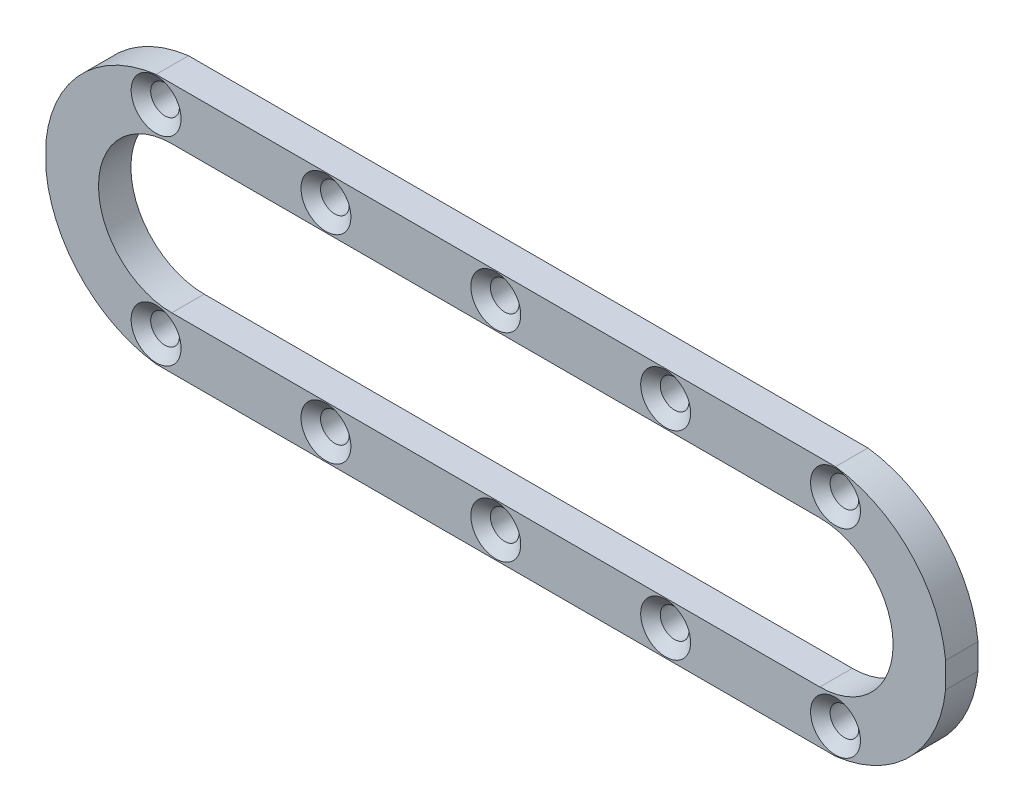
SolidWorks part; units mm, degrees
ref_plane "Front" through (0, 0, 0) normal (0, 0, 1) x (1, 0, 0)
ref_plane "Top" through (0, 0, 0) normal (0, 1, 0) x (1, 0, 0)
ref_plane "Right" through (0, 0, 0) normal (1, 0, 0) x (0, 0, -1)
sketch "Sketch1" plane through (0, 0, 0) normal (0, 0, 1) x (1, 0, 0)
  line L1 (88.138, 24.5745) -> (-88.138, 24.5745)
  line L2 (88.138, 24.5745) -> (88.138, -24.5745)
  line L3 (88.138, -24.5745) -> (-88.138, -24.5745)
  line L4 (-88.138, 24.5745) -> (-88.138, -24.5745)
  line L5 (88.138, 24.5745) -> (-88.138, -24.5745) construction
  line L6 (88.138, -24.5745) -> (-88.138, 24.5745) construction
  point P0 (0, 0)
  dimension "D1" = 176.276
  dimension "D2" = 49.149
extrude "Boss-Extrude1" add sketch "Sketch1" along normal blind 6.35
sketch "Sketch2" plane through (0, 0, 6.35) normal (0, 0, 1) x (1, 0, 0)
  line L0 (63.5, 0) -> (-63.5, 0) construction
  line L1 (63.5, -14.351) -> (-63.5, -14.351)
  line L2 (63.5, 14.351) -> (-63.5, 14.351)
  arc A0 (63.5, -14.351) -> (63.5, 14.351) centre (63.5, 0) ccw
  arc A1 (-63.5, 14.351) -> (-63.5, -14.351) centre (-63.5, 0) ccw
  point P2 (0, 0)
  dimension "D1" = 127
  dimension "D2" = 28.702
extrude "Cut-Extrude1" cut sketch "Sketch2" against normal through all
sketch "Sketch8" plane through (0, 0, 6.35) normal (0, 0, 1) x (1, 0, 0)
  line L4 (-63.5, 24.765) -> (63.5, 24.765)
  line L5 (-63.5, 14.351) -> (63.5, 14.351)
  line L6 (-63.5, -14.351) -> (63.5, -14.351)
  line L7 (-63.5, -24.765) -> (63.5, -24.765)
  arc A5 (-63.5, 14.351) -> (-63.5, -14.351) centre (-63.5, 0) ccw
  arc A6 (-63.5, 24.765) -> (-63.5, -24.765) centre (-63.5, 0) ccw
  arc A7 (63.5, 14.351) -> (63.5, -14.351) centre (63.5, 0) cw
  arc A8 (63.5, 24.765) -> (63.5, -24.765) centre (63.5, 0) cw
  line M5 (-88.138, 24.5745) -> (-88.138, -24.5745)
  line M6 (-88.138, -24.5745) -> (88.138, -24.5745)
  line M7 (88.138, -24.5745) -> (88.138, 24.5745)
  line M8 (88.138, 24.5745) -> (-88.138, 24.5745)
  dimension "D1" = 10.414
  dimension "D2" = 10.414
extrude "Cut-Extrude4" cut sketch "Sketch8" against normal through all contours A6 M8 M5 | A6 M5 M6 | A8 M8 M7 | A8 M7 M6 region at (-82.8086, 19.1871, 6.35) region at (82.8086, 19.1871, 6.35) region at (-82.8086, -19.1871, 6.35) region at (82.8086, -19.1871, 6.35)
sketch "Sketch12" plane through (0, 0, 6.35) normal (0, 0, 1) x (1, 0, 0)
  circle A0 centre (-33.2829, 19.4627) radius 2.5527
  circle A1 centre (-66.5658, 19.4627) radius 2.5527
  circle A2 centre (0, 19.4627) radius 2.5527
  circle A3 centre (66.5658, 19.4627) radius 2.5527
  circle A4 centre (33.2829, 19.4628) radius 2.5527
  circle A5 centre (0, -19.4627) radius 2.5527
  circle A6 centre (-33.2829, -19.4627) radius 2.5527
  circle A7 centre (-66.5658, -19.4627) radius 2.5527
  circle A8 centre (33.2829, -19.4627) radius 2.5527
  circle A9 centre (66.5658, -19.4627) radius 2.5527
  dimension "D1" = 5.1054
hole_wizard "CSK for #10 Flat Head Machine Screw (100)2" positions "Sketch15" profile "Sketch16" countersink size "#10" standard "ANSI Inch" end condition through all
sketch "Sketch15" plane through (0, 0, 6.35) normal (0, 0, 1) x (1, 0, 0)
  point P0 (-66.5658, 19.4627)
  point P3 (-33.2829, 19.4627)
  point P6 (0, 19.4627)
  point P9 (33.2829, 19.4628)
  point P12 (66.5658, 19.4627)
  point P15 (66.5658, -19.4627)
  point P18 (33.2829, -19.4627)
  point P21 (0, -19.4627)
  point P24 (-33.2829, -19.4627)
  point P27 (-66.5658, -19.4627)
sketch "Sketch16" plane through (-66.5658, 19.4627, 6.35) normal (1, 0, 0) x (0, -1, 0)
  line L0 (0, 0) -> (0, 6.35)
  line L1 (0, 6.35) -> (2.8067, 6.35)
  line L2 (2.8067, 6.35) -> (2.8067, 1.7477)
  line L3 (2.8067, 1.7477) -> (4.8895, 0)
  line L5 (4.8895, 0) -> (0, 0)
  line L6 (-2.8067, 1.7477) -> (-4.8895, 0) construction
  line L11 (0, -6.35) -> (0, 107.95) construction
  dimension "Thru Hole Dia." = 5.6134
  dimension "Thru Hole Depth" = 6.35
  dimension "Near C'Sink Dia." = 9.779
  dimension "Near C'Sink Angle" = 100
